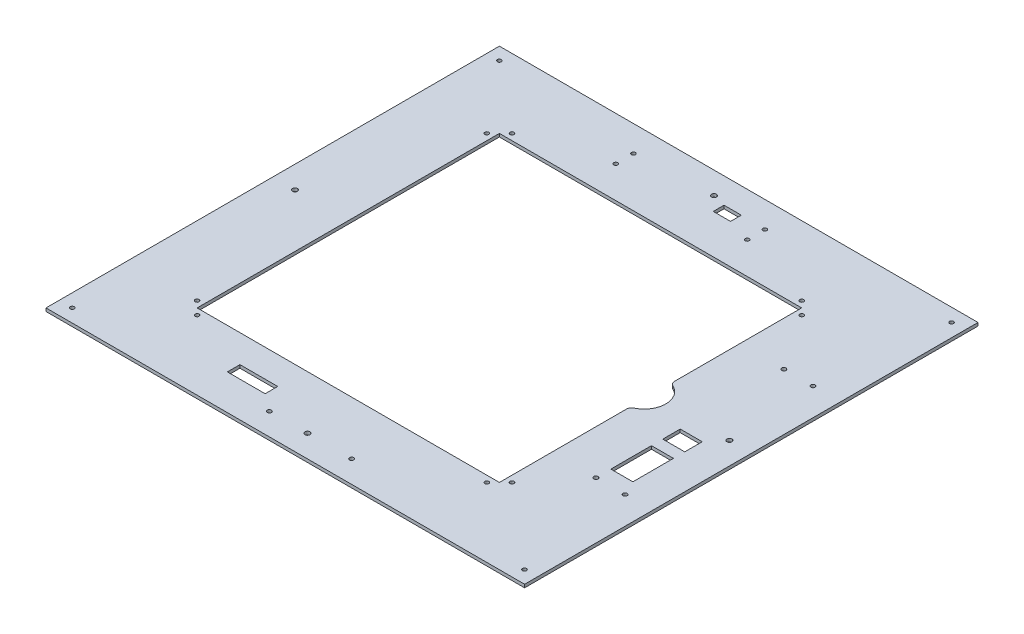
SolidWorks part; units mm, degrees
ref_plane "Front" through (0, 0, 0) normal (0, 0, 1) x (1, 0, 0)
ref_plane "Top" through (0, 0, 0) normal (0, 1, 0) x (1, 0, 0)
ref_plane "Right" through (0, 0, 0) normal (1, 0, 0) x (0, 0, -1)
sketch "Sketch1" plane through (0, 0, 0) normal (0, 1, 0) x (1, 0, 0)
  line L0 (-55, 0) -> (55, 0) construction
  line L1 (-242.5515, 228.6) -> (240.0485, 228.6)
  line L2 (-242.5515, 228.6) -> (-242.5515, -228.6)
  line L3 (-242.5515, -228.6) -> (240.0485, -228.6)
  line L4 (240.0485, 228.6) -> (240.0485, -228.6)
  line L5 (-242.5515, 228.6) -> (240.0485, -228.6) construction
  line L6 (-242.5515, -228.6) -> (240.0485, 228.6) construction
  line L7 (-166.3515, 152.4) -> (138.4485, 152.4)
  line L8 (-166.3515, 152.4) -> (-166.3515, -152.4)
  line L9 (-166.3515, -152.4) -> (138.4485, -152.4)
  line L11 (-166.3515, 152.4) -> (138.4485, -152.4) construction
  line L12 (-166.3515, -152.4) -> (138.4485, 152.4) construction
  line L13 (-160.0015, 146.05) -> (132.0985, 146.05)
  line L14 (-160.0015, 146.05) -> (-160.0015, -146.05)
  line L15 (-160.0015, -146.05) -> (132.0985, -146.05)
  line L16 (132.0985, 146.05) -> (132.0985, -146.05)
  line L17 (-160.0015, 146.05) -> (132.0985, -146.05) construction
  line L18 (-160.0015, -146.05) -> (132.0985, 146.05) construction
  line L19 (-166.3515, -152.4) -> (-140.9515, -152.4)
  line L23 (-242.5515, 0) -> (240.0485, 0) construction
  line L28 (182.9854, -43.6118) -> (205.1825, -43.6118)
  line L29 (182.9854, -43.6118) -> (182.9854, -84.5553)
  line L30 (182.9854, -84.5553) -> (205.1825, -84.5553)
  line L31 (205.1825, -43.6118) -> (205.1825, -84.5553)
  line L32 (182.9854, -32.247) -> (205.1825, -32.247)
  line L33 (182.9854, -32.247) -> (182.9854, -14.612)
  line L34 (182.9854, -14.612) -> (205.1825, -14.612)
  line L35 (205.1825, -32.247) -> (205.1825, -14.612)
  line L40 (27.0379, 202.954) -> (9.5991, 202.954)
  line L41 (27.0379, 202.954) -> (27.0379, 192.0704)
  line L42 (27.0379, 192.0704) -> (9.5991, 192.0704)
  line L43 (9.5991, 202.954) -> (9.5991, 192.0704)
  line L44 (-95.2315, -180.3456) -> (-57.1315, -180.3456)
  line L45 (-95.2315, -180.3456) -> (-95.2315, -193.0456)
  line L46 (-95.2315, -193.0456) -> (-57.1315, -193.0456)
  line L47 (-57.1315, -180.3456) -> (-57.1315, -193.0456)
  line L50 (138.4485, -20.7413) -> (138.4485, -152.4)
  line L51 (138.4485, 20.7413) -> (138.4485, 152.4)
  circle A0 centre (51.3519, 202.311) radius 2
  circle A1 centre (51.3519, 184.531) radius 2
  circle A2 centre (-81.1091, 202.311) radius 2
  circle A3 centre (-81.1091, 184.531) radius 2
  circle A4 centre (212.3904, -99.5798) radius 2.0955
  circle A5 centre (212.3904, 89.828) radius 2.0955
  circle A6 centre (-39.6436, -206.2861) radius 2.1
  circle A7 centre (43.3382, -206.2861) radius 2.1
  circle A8 centre (-172.7335, 146.082) radius 2
  circle A9 centre (-160.0335, 158.782) radius 2
  circle A12 centre (-160.0335, -158.782) radius 2
  circle A13 centre (-172.7335, -146.082) radius 2
  circle A14 centre (132.1305, 158.782) radius 2
  circle A15 centre (144.8305, 146.082) radius 2
  circle A16 centre (144.8305, -146.082) radius 2
  circle A17 centre (132.1305, -158.782) radius 2
  circle A18 centre (-229.8327, 215.8812) radius 2
  circle A19 centre (226.7201, 215.2716) radius 2
  circle A20 centre (-229.3755, -215.2716) radius 2
  circle A21 centre (227.2281, -215.9066) radius 2
  circle A22 centre (-220.0871, 0) radius 2.54
  circle A23 centre (-1.2915, -206.2372) radius 2.54
  circle A24 centre (-3.8315, 206.2626) radius 2.54
  circle A25 centre (217.7111, 0.294) radius 2.54
  circle A26 centre (182.9854, -99.5798) radius 2.159
  circle A28 centre (182.9854, 89.828) radius 2.159
  arc A31 (138.4485, 20.7413) -> (138.4485, -20.7413) centre (132.0985, 0) cw
  point P0 (-1.2515, 0)
  point P6 (-44.5662, -1.1741)
  point P11 (-84.1987, 3.6789)
  point P21 (-13.9515, 0)
  point P22 (-13.9515, 0)
  point P23 (-1.2515, 0)
  point P94 (0, 0)
  dimension "D15" = 4
  dimension "D16" = 4
  dimension "D17" = 26.289
  dimension "D18" = 17.78
  dimension "D19" = 188.6966
  dimension "D20" = 132.461
  dimension "D22" = 27.6581
  dimension "D23" = 4.191
  dimension "D24" = 129.0202
  dimension "D26" = 4.2
  dimension "D27" = 22.3139
  dimension "D28" = 202.9079
  dimension "D29" = 82.9818
  dimension "D33" = 69.818
  dimension "D34" = 82.518
  dimension "D35" = 4
  dimension "D36" = 69.818
  dimension "D37" = 82.518
  dimension "D38" = 4
  dimension "D39" = 107.918
  dimension "D40" = 69.818
  dimension "D41" = 95.218
  dimension "D42" = 82.518
  dimension "D43" = 95.218
  dimension "D44" = 82.518
  dimension "D45" = 69.818
  dimension "D46" = 107.918
  dimension "D47" = 4
  dimension "D48" = 4
  dimension "D49" = 4
  dimension "D50" = 4
  dimension "D51" = 12.7188
  dimension "D53" = 13.3284
  dimension "D54" = 13.3284
  dimension "D55" = 13.176
  dimension "D56" = 13.3284
  dimension "D57" = 4
  dimension "D58" = 4
  dimension "D59" = 4
  dimension "D60" = 12.8204
  dimension "D61" = 4
  dimension "D62" = 12.6934
  dimension "D63" = 22.4644
  dimension "D65" = 22.3628
  dimension "D66" = 241.26
  dimension "D67" = 5.08
  dimension "D68" = 5.08
  dimension "D69" = 5.08
  dimension "D70" = 22.3374
  dimension "D71" = 238.72
  dimension "D72" = 22.3374
  dimension "D73" = 228.306
  dimension "D74" = 5.08
  dimension "D1" = 457.2
  dimension "D2" = 482.6
  dimension "D3" = 304.8
  dimension "D4" = 304.8
  dimension "D5" = 76.2
  dimension "D6" = 292.1
  dimension "D7" = 146.05
  dimension "D8" = 228.6
  dimension "D21" = 17.78
  dimension "D25" = 189.4078
  dimension "D30" = 12.7
  dimension "D31" = 185.42
  dimension "D32" = 38.1
  dimension "D52" = 12.7188
extrude "Boss-Extrude1" add sketch "Sketch1" along normal blind 3.175 contours L4 L1 L2 L3 L7 L9 L8 region at (-1.2515, 0, -221.9522)
fillet "Fillet2" radius 5 2 edges at (138.4485, 1.5875, 20.7413) (138.4485, 1.5875, -20.7413)
